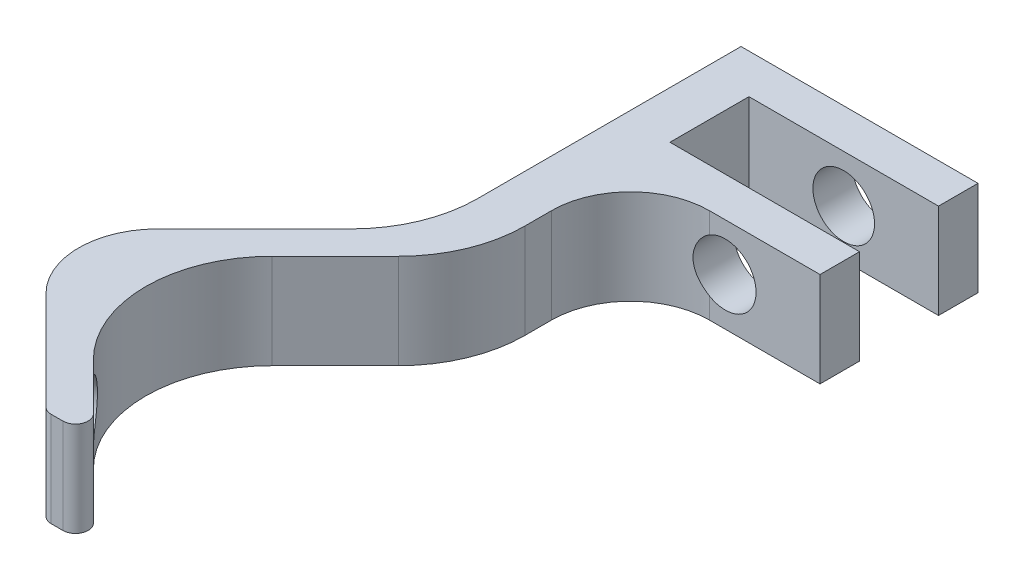
SolidWorks part; units mm, degrees
ref_plane "Alzado" through (0, 0, 0) normal (0, 0, 1) x (1, 0, 0)
ref_plane "Planta" through (0, 0, 0) normal (0, 1, 0) x (1, 0, 0)
ref_plane "Vista lateral" through (0, 0, 0) normal (1, 0, 0) x (0, 0, -1)
sketch "Croquis1" plane through (0, 0, 0) normal (0, 1, 0) x (1, 0, 0)
  line L14 (0, 0) -> (0, 20)
  line L15 (0, 20) -> (15, 20)
  line L16 (15, 20) -> (15, 17.5)
  line L17 (15, 17.5) -> (3, 17.5)
  line L18 (3, 17.5) -> (3, 12.5)
  line L19 (3, 12.5) -> (15, 12.5)
  line L20 (15, 12.5) -> (15, 10)
  line L21 (15, 10) -> (3, 10)
  line L22 (3, 10) -> (3, 0)
  line L23 (3, 0) -> (0, 0)
  line L24 (0, 0) -> (-12, -12)
  line L25 (-12, -12) -> (-9, -12)
  line L26 (-9, -12) -> (3, 0)
  line L27 (-12, -12) -> (-2, -22)
  line L28 (-2, -22) -> (1, -22)
  line L29 (1, -22) -> (-9, -12)
  line L30 (0, 0) -> (3, 0)
  point P3 (0, 0)
  dimension "D1" = 15
  dimension "D2" = 2.5
  dimension "D3" = 5
  dimension "D4" = 20
  dimension "D5" = 3
  dimension "D6" = 12
  dimension "D7" = 45
  dimension "D8" = 90
  dimension "D9" = 10
extrude "Saliente-Extruir1" add sketch "Croquis1" along normal blind 6 contours L25 L26 L23 L24 | L23 L22 L21 L20 L19 L18 L17 L16 L15 L14 | L28 L29 L25 L27 region at (0.25, 0, -10) region at (-4.5, 0, 6) region at (-5.5, 0, 17)
fillet "Redondeo1" radius 8 1 edges at (-9, 3, 12)
fillet "Redondeo2" radius 5 1 edges at (-12, 3, 12)
fillet "Redondeo3" radius 8 2 edges at (0, 3, 0) (3, 3, 0)
fillet "Redondeo4" radius 0.8 2 edges at (-2, 3, 22) (1, 3, 22)
sketch "Croquis2" plane through (-10.5, 0, 10.5) normal (0.7071, 0, -0.7071) x (-0.7071, 0, -0.7071)
  line L0 (-14.3321, 6) -> (-14.3321, 0) construction
  line L1 (-14.3321, 6) -> (-14.3321, 0) construction
  circle A0 centre (-10.3321, 3) radius 1.9
  point P2 (-11.0879, 2.8762)
  point P3 (0, 0)
  point P6 (-14.3321, 3)
  dimension "D1" = 3.8
  dimension "D2" = 4
extrude "Cortar-Extruir1" cut sketch "Croquis2" against normal blind 6 and the other way blind 6
fillet "Redondeo5" radius 5 1 edges at (3, 3, -10)
sketch "Croquis3" plane through (0, 0, -12.5) normal (0, 0, -1) x (-1, 0, 0)
  line L0 (-15, 6) -> (-15, 0) construction
  circle A0 centre (-9, 3) radius 1.95
  point P4 (-15, 3)
  dimension "D2" = 3.9
  dimension "D1" = 6
extrude "Cortar-Extruir2" cut sketch "Croquis3" along normal through all and the other way blind 10 contours A0
